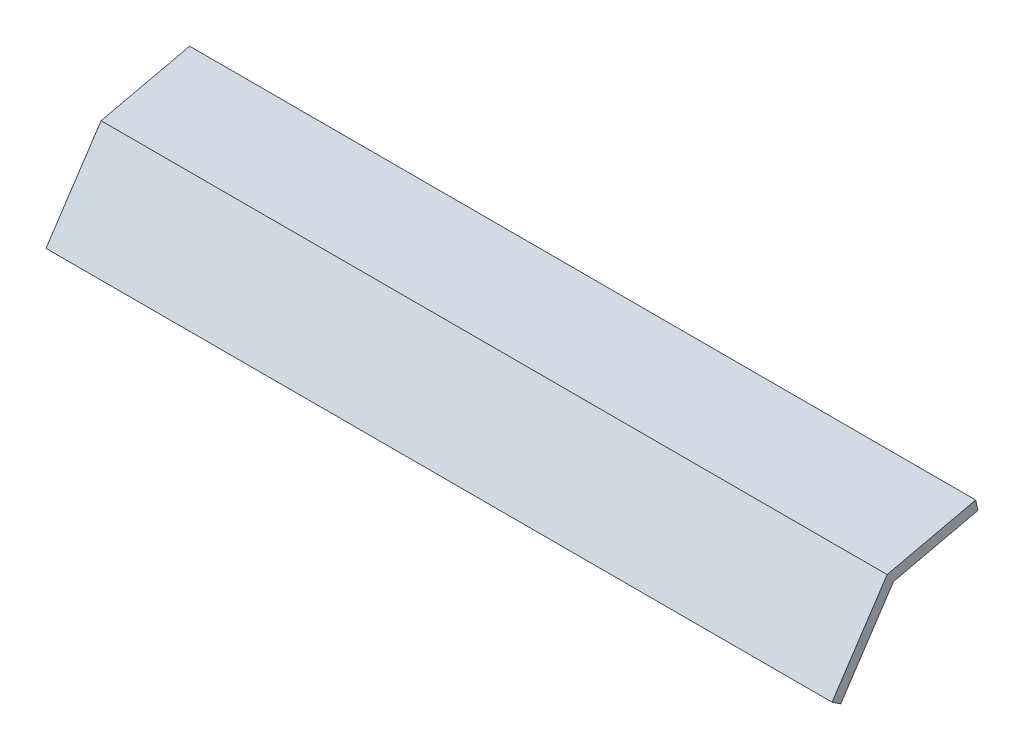
SolidWorks part; units mm, degrees
ref_plane "Front Plane" through (0, 0, 0) normal (0, 0, 1) x (1, 0, 0)
ref_plane "Top Plane" through (0, 0, 0) normal (0, 1, 0) x (1, 0, 0)
ref_plane "Right Plane" through (0, 0, 0) normal (1, 0, 0) x (0, 0, -1)
sketch "Sketch1" plane through (0, 0, 0) normal (1, 0, 0) x (0, 0, -1)
  line L0 (0, 0) -> (16.7984, 25.3043)
  line L1 (16.7984, 25.3043) -> (43.7982, 31.4997)
  line L2 (43.7982, 31.4997) -> (44.5083, 28.4051)
  line L3 (44.5083, 28.4051) -> (18.743, 22.493)
  line L4 (18.743, 22.493) -> (2.6452, -1.756)
  line L5 (2.6452, -1.756) -> (0, 0)
  line L6 (18.743, 22.493) -> (44.5083, 28.4051) construction
  line L7 (2.6452, -1.756) -> (18.743, 22.493) construction
  point P3 (16.0727, 13.9568)
  point P8 (9.4077, 6.4929)
  point P9 (31.4994, 27.0332)
  point P10 (39.8605, 22.465)
  point P12 (17.2917, 16.1387)
  dimension "D1" = 3.175
  dimension "D2" = 3.175
extrude "Boss-Extrude1" add sketch "Sketch1" along normal mid plane 239.7125
